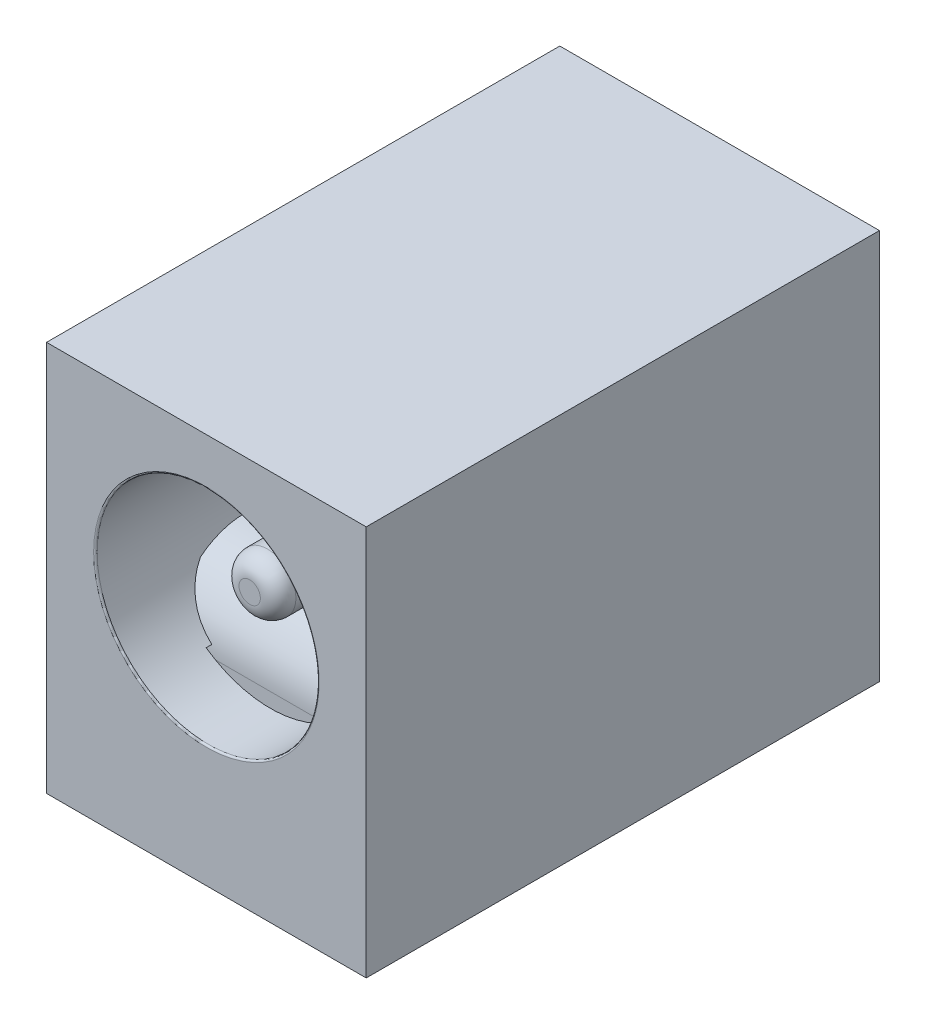
SolidWorks part; units mm, degrees
ref_plane "Plano frontal" through (0, 0, 0) normal (0, 0, 1) x (1, 0, 0)
ref_plane "Plano superior" through (0, 0, 0) normal (0, 1, 0) x (1, 0, 0)
ref_plane "Plano direito" through (0, 0, 0) normal (1, 0, 0) x (0, 0, -1)
sketch "Esboço1" plane through (0, 0, 0) normal (1, 0, 0) x (0, 0, -1)
  line L1 (-7.225, -5.5) -> (7.225, -5.5)
  line L2 (-7.225, -5.5) -> (-7.225, 5.5)
  line L3 (-7.225, 5.5) -> (7.225, 5.5)
  line L4 (7.225, -5.5) -> (7.225, 5.5)
  line L5 (-7.225, -5.5) -> (7.225, 5.5) construction
  line L6 (-7.225, 5.5) -> (7.225, -5.5) construction
  point P0 (0, 0)
  dimension "D1" = 11
  dimension "D2" = 14.45
extrude "Ressalto-extrusão1" add sketch "Esboço1" along normal blind 9
sketch "Esboço3" plane through (0, 0, 7.225) normal (0, 0, 1) x (1, 0, 0)
  line L0 (4.5, 5.5) -> (4.5, 4.175) construction
  line L1 (9, 5.5) -> (0, 5.5) construction
  line L3 (4.5, 1.05) -> (4.5, 5.5) construction
  circle A0 centre (4.5, 1.05) radius 3.125
  dimension "D1" = 6.25
  dimension "D2" = 4.45
extrude "Corte-extrusão2" cut sketch "Esboço3" against normal blind 8.93
sketch "Esboço4" plane through (0, 0, -1.705) normal (0, 0, 1) x (1, 0, 0)
  circle A2 centre (4.5, 1.05) radius 0.8
  dimension "D1" = 1.6
extrude "Ressalto-extrusão2" add sketch "Esboço4" along normal blind 7.71
fillet "Filete1" radius 0.5 1 edges at (5.3, 1.05, 6.005)
fillet "Filete2" radius 0.05 1 edges at (7.625, 1.05, 7.225)
sketch "Esboço5" plane through (0, -5.5, 0) normal (0, -1, 0) x (1, 0, 0)
  line L0 (4.5, 7.225) -> (4.5, 5.425) construction
  line L1 (9, 7.225) -> (0, 7.225) construction
  line L2 (1.5, 5.425) -> (7.5, 5.425)
  line L3 (1.5, 5.425) -> (1.5, -0.575)
  line L4 (1.5, -0.575) -> (7.5, -0.575)
  line L5 (7.5, -0.575) -> (7.5, 5.425)
  point P7 (4.5, 5.425)
  dimension "D1" = 1.8
  dimension "D2" = 6
  dimension "D3" = 6
extrude "Corte-extrusão5" cut sketch "Esboço5" against normal blind 4
sketch "Esboço7" plane through (0, -1.5, 0) normal (0, -1, 0) x (1, 0, 0)
  line L0 (4.5, 5.425) -> (4.5, -0.575) construction
  line L1 (7.5, 5.425) -> (1.5, 5.425) construction
  line L2 (1.5, -0.575) -> (7.5, -0.575) construction
  line L4 (1.6557, -0.4399) -> (7.3443, -0.4399)
  line L5 (1.6557, -0.4399) -> (1.6557, 5.2899)
  line L6 (1.6557, 5.2899) -> (7.3443, 5.2899)
  line L7 (7.3443, -0.4399) -> (7.3443, 5.2899)
  line L8 (1.6557, -0.4399) -> (7.3443, 5.2899) construction
  line L9 (1.6557, 5.2899) -> (7.3443, -0.4399) construction
  point P6 (4.5, 2.425)
extrude "Ressalto-extrusão4" add sketch "Esboço7" along normal blind 4 and the other way blind 1.7
fillet "Filete5" radius 2 1 edges at (4.5, 0.2, 5.2899)
chamfer "Chanfro4" distance 2 angle 45 1 edges at (4.5, 0.2, -0.4399)
fillet "Filete6" [suppressed] radius 1
sketch "Esboço9" [suppressed] plane through (0, -5.5, 0) normal (0, -1, 0) x (1, 0, 0)
  line L0 (4.5, 5.425) -> (4.5, -0.575) construction
  line L1 (7.5, 5.425) -> (1.5, 5.425) construction
  line L2 (1.5, -0.575) -> (7.5, -0.575) construction
  line L4 (1.9457, -0.3154) -> (7.0543, -0.3154)
  line L5 (1.9457, -0.3154) -> (1.9457, 5.1654)
  line L6 (1.9457, 5.1654) -> (7.0543, 5.1654)
  line L7 (7.0543, -0.3154) -> (7.0543, 5.1654)
  line L8 (1.9457, -0.3154) -> (7.0543, 5.1654) construction
  line L9 (1.9457, 5.1654) -> (7.0543, -0.3154) construction
  line L10 (1.5, -0.575) -> (7.5, -0.575)
  line L11 (1.5, -0.575) -> (1.5, 5.425)
  line L12 (1.5, 5.425) -> (7.5, 5.425)
  line L13 (7.5, -0.575) -> (7.5, 5.425)
  line L14 (1.5, -0.575) -> (7.5, 5.425) construction
  line L15 (1.5, 5.425) -> (7.5, -0.575) construction
  point P6 (4.5, 2.425)
  point P11 (4.5, 2.425)
extrude "Corte-extrusão6" [suppressed] cut sketch "Esboço9" against normal blind 4
sketch "Esboço11" [suppressed] plane through (0, -5.5, 0) normal (0, -1, 0) x (1, 0, 0)
  line L0 (4.5, 5.425) -> (4.5, -0.575) construction
  line L1 (7.5, 5.425) -> (1.5, 5.425) construction
  line L2 (1.5, -0.575) -> (7.5, -0.575) construction
  line L4 (1.323, -0.7753) -> (7.677, -0.7753)
  line L5 (1.323, -0.7753) -> (1.323, 5.6253)
  line L6 (1.323, 5.6253) -> (7.677, 5.6253)
  line L7 (7.677, -0.7753) -> (7.677, 5.6253)
  line L8 (1.323, -0.7753) -> (7.677, 5.6253) construction
  line L9 (1.323, 5.6253) -> (7.677, -0.7753) construction
  line L10 (1.9457, -0.3154) -> (7.0543, -0.3154)
  line L11 (1.9457, -0.3154) -> (1.9457, 5.1654)
  line L12 (1.9457, 5.1654) -> (7.0543, 5.1654)
  line L13 (7.0543, -0.3154) -> (7.0543, 5.1654)
  line L14 (1.9457, -0.3154) -> (7.0543, 5.1654) construction
  line L15 (1.9457, 5.1654) -> (7.0543, -0.3154) construction
  point P6 (4.5, 2.425)
  point P11 (4.5, 2.425)
extrude "Corte-extrusão7" [suppressed] cut sketch "Esboço11" against normal blind 5.7
sketch "Esboço13" [suppressed] plane through (0, 0, -7.225) normal (0, 0, -1) x (-1, 0, 0)
  line L0 (-11.3238, 1.01) -> (-10.8452, 6.8292)
  line L1 (-6.725, 5.04) -> (-2.275, 5.04)
  line L2 (-0.525, 1.01) -> (1.1221, 1.01)
  line L4 (-6.725, 5.04) -> (-2.275, 5.04)
  line L5 (-10.8452, 6.8292) -> (1.0427, 6.9871)
  line L8 (1.1221, 1.01) -> (1.0427, 6.9871)
  line L12 (-8.475, 1.01) -> (-11.3238, 1.01)
  line L13 (-2.275, 5.04) -> (-0.525, 1.01)
  line L14 (-6.725, 5.04) -> (-8.475, 1.01)
  point P3 (-4.5, 5.04)
  point P10 (-4.5, 5.04)
  dimension "D1" = 4.45
extrude "Corte-extrusão14" [suppressed] cut sketch "Esboço13" against normal blind 11.17 contours L14 L1 L13 L2 L0 L12
sketch "Esboço14" [suppressed] plane through (0, 5.5, 0) normal (0, 1, 0) x (1, 0, 0)
  line L3 (7, -5.01) -> (10.2146, -5.01)
  line L4 (-1.2146, -6.16) -> (2, -6.16)
  line L5 (-1.2146, -6.16) -> (-1.2146, -5.01)
  line L6 (-1.2146, -5.01) -> (2, -5.01)
  line L7 (10.2146, -6.16) -> (10.2146, -5.01)
  line L11 (2, -6.16) -> (2, -5.01)
  line L13 (7, -6.16) -> (7, -5.01)
  line L18 (7, -6.16) -> (10.2146, -6.16)
  point P6 (4.5, -5.585)
  point P11 (4.5, -5.585)
  dimension "D2" = 1.15
extrude "Corte-extrusão15" [suppressed] cut sketch "Esboço14" against normal blind 1
sketch "Esboço16" [suppressed] plane through (0, 0, -7.225) normal (0, 0, -1) x (-1, 0, 0)
  line L0 (-8.475, 1.01) -> (-8.475, 1.5435)
  line L1 (-8.475, 1.01) -> (-0.525, 1.01)
  line L2 (-0.525, 1.01) -> (-0.525, 1.5435)
  line L3 (-6.725, 5.04) -> (-8.475, 1.5435)
  line L4 (-6.725, 5.04) -> (-2.275, 5.04)
  line L6 (-2.275, 5.04) -> (-0.525, 1.5435)
extrude "Ressalto-extrusão5" [suppressed] add sketch "Esboço16" against normal blind 11.3
fillet "Filete7" [suppressed] radius 0.08
sketch "Esboço17" [suppressed] plane through (0, 0, 4.075) normal (0, 0, 1) x (1, 0, 0)
  line L0 (1.3762, 0.9625) -> (3.7048, 0.9625)
  line L1 (7.6219, 0.9102) -> (5.2786, 0.8664)
  arc A0 (7.6219, 0.9102) -> (1.3762, 0.9625) centre (4.5, 1.05) ccw
  arc A1 (5.2786, 0.8664) -> (3.7048, 0.9625) centre (4.5, 1.05) ccw
extrude "Corte-extrusão17" [suppressed] cut sketch "Esboço17" against normal blind 5.8
sketch "Esboço18" [suppressed] plane through (0, 0, -7.225) normal (0, 0, -1) x (-1, 0, 0)
  line L0 (-11.3995, -1.69) -> (1.4949, -1.69)
  line L1 (-8.92, -5.5) -> (-0.08, -5.5) construction
  line L2 (-11.3995, -1.69) -> (-11.0487, 7.356)
  line L3 (-11.0487, 7.356) -> (1.4949, 8.0327)
  line L4 (1.4949, 8.0327) -> (1.4949, -1.69)
  dimension "D1" = 3.81
extrude "Corte-extrusão18" [suppressed] cut sketch "Esboço18" against normal blind 0.97
sketch "Esboço19" [suppressed] plane through (0, 0, -6.255) normal (0, 0, -1) x (-1, 0, 0)
  line L0 (-8.92, -5.5) -> (-0.08, -5.5) construction
  line L1 (-5.995, -10.5806) -> (-3.005, -10.5806)
  line L2 (-5.995, -10.5806) -> (-5.995, -0.4194)
  line L3 (-5.995, -0.4194) -> (-3.005, -0.4194)
  line L4 (-3.005, -10.5806) -> (-3.005, -0.4194)
  line L5 (-5.995, -10.5806) -> (-3.005, -0.4194) construction
  line L6 (-5.995, -0.4194) -> (-3.005, -10.5806) construction
  point P0 (-4.5, -5.5)
  dimension "D1" = 2.99
extrude "Corte-extrusão19" [suppressed] cut sketch "Esboço19" along normal blind 0.97
sketch "Esboço20" [suppressed] plane through (0, 0, -6.255) normal (0, 0, -1) x (-1, 0, 0)
  line L3 (-5.825, -8.8251) -> (-3.175, -8.8251)
  line L4 (-5.825, -8.8251) -> (-5.825, -0.787)
  line L6 (-3.175, -8.8251) -> (-3.175, -0.787)
  arc A0 (-3.175, -0.787) -> (-5.825, -0.787) centre (-4.5, 1.05) ccw
  point P5 (-4.5, -2.5751)
  dimension "D3" = 4.53
  dimension "D2" = 2.65
extrude "Ressalto-extrusão6" [suppressed] add sketch "Esboço20" along normal blind 0.32
fillet "Filete8" [suppressed] radius 0.08
fillet "Filete9" [suppressed] radius 0.2
sketch "Esboço21" [suppressed] plane through (0, 0, -6.575) normal (0, 0, -1) x (-1, 0, 0)
  circle A0 centre (-4.4893, 1.1326) radius 1.3
  dimension "D1" = 2.6
extrude "Corte-extrusão20" [suppressed] cut sketch "Esboço21" against normal blind 0.22
chamfer "Chanfro5" [suppressed] distance 0.1 angle 45
sketch "Esboço22" [suppressed] plane through (0, 0, -6.355) normal (0, 0, -1) x (-1, 0, 0)
  circle A0 centre (-4.4893, 1.1326) radius 1.1934
extrude "Ressalto-extrusão8" [suppressed] add sketch "Esboço22" along normal blind 0.4
sketch "Esboço23" [suppressed] plane through (0, 0, -6.755) normal (0, 0, -1) x (-1, 0, 0)
  circle A0 centre (-4.4893, 1.1326) radius 0.5951
extrude "Corte-extrusão21" [suppressed] cut sketch "Esboço23" against normal blind 0.8
draft "Inclinação8" [suppressed] type of draft neutral plane draft angle 35 faces to draft 1 parameters "D1"=35
sketch "Esboço24" [suppressed] plane through (0, 0, -6.575) normal (0, 0, -1) x (-1, 0, 0)
  line L2 (-5.825, -6.8251) -> (-7.3072, -6.9926)
  line L4 (-7.3072, -6.9926) -> (-7.0269, -7.7009)
  line L5 (-7.0269, -7.7009) -> (-5.825, -7.8251)
  line L6 (-3.161, -6.8251) -> (-1.7002, -7.1697)
  line L8 (-5.825, -8.8251) -> (-5.825, -0.787) construction
  line L10 (-1.7002, -7.1697) -> (-2.4306, -7.5238)
  line L11 (-2.4306, -7.5238) -> (-2.5017, -7.8251)
  line L12 (-2.5017, -7.8251) -> (-3.161, -7.8251)
  arc A0 (-3.161, -6.8251) -> (-3.161, -7.8251) centre (-2.6839, -7.3251) ccw
  arc A1 (-5.825, -6.8251) -> (-5.825, -7.8251) centre (-6.35, -7.3251) cw
  point P0 (-4.5037, -7.3251)
extrude "Corte-extrusão22" [suppressed] cut sketch "Esboço24" against normal blind 0.8
sketch "Esboço26" [suppressed] plane through (0, 0, -6.575) normal (0, 0, -1) x (-1, 0, 0)
  line L0 (-5.825, -7.8251) -> (-4.5, -8.8251)
  line L1 (-3.175, -8.8251) -> (-5.825, -8.8251) construction
  line L2 (-3.175, -7.8114) -> (-4.5, -8.8251)
  line L3 (-5.825, -7.8251) -> (-7.9617, -7.8251)
  line L4 (-7.9617, -7.8251) -> (-7.2712, -9.4826)
  line L5 (-7.2712, -9.4826) -> (-3.8361, -10.0138)
  line L6 (-3.8361, -10.0138) -> (-2.335, -9.3883)
  line L7 (-2.335, -9.3883) -> (-1.7907, -8.0667)
  line L8 (-1.7907, -8.0667) -> (-3.175, -7.8114)
extrude "Corte-extrusão23" [suppressed] cut sketch "Esboço26" against normal blind 0.8
sketch "Esboço27" [suppressed] plane through (0, 0, -6.575) normal (0, 0, -1) x (-1, 0, 0)
  line L0 (-4.5, 3.115) -> (-4.5, -8.8251) construction
  line L1 (-4.5, -8.8251) -> (-4.2386, -8.6251) construction
  arc A0 (-3.375, -0.6816) -> (-5.625, -0.6816) centre (-4.5, 1.05) ccw construction
  circle A1 centre (-4.5, -3.285) radius 0.4953
  arc A2 (-3.175, -0.787) -> (-5.825, -0.787) centre (-4.5, 1.05) ccw construction
  point P13 (-4.5, 3.315)
  dimension "D1" = 6.6
  dimension "D2" = 0.9907
extrude "Corte-extrusão24" [suppressed] cut sketch "Esboço27" against normal blind 1.3
fillet "Filete10" [suppressed] radius 0.2
sketch "Esboço28" [suppressed] plane through (0, 0, 0) normal (-1, 0, 0) x (0, 0, 1)
  line L1 (-5.4377, -1.8018) -> (-3.4377, -1.8018)
  line L2 (-5.4377, -1.8018) -> (-5.4377, -1.6304)
  line L3 (-5.4377, -1.6304) -> (-3.4377, -1.6304)
  line L4 (-3.4377, -1.8018) -> (-3.4377, -1.6304)
  line L5 (-5.4377, -1.8018) -> (-3.4377, -1.6304) construction
  line L6 (-5.4377, -1.6304) -> (-3.4377, -1.8018) construction
  point P0 (-4.4377, -1.7161)
  dimension "D1" = 2
extrude "Ressalto-extrusão9" [suppressed] add sketch "Esboço28" along normal blind 0.005
sketch "Esboço29" [suppressed] plane through (0, 0, 0) normal (-1, 0, 0) x (0, 0, 1)
  line L0 (-4.4377, -1.7161) -> (-4.4377, -1.8018) construction
  line L2 (-5.4377, -1.8018) -> (-3.4377, -1.8018) construction
  line L4 (-5.4527, -1.8161) -> (-3.4227, -1.8161)
  line L5 (-5.4527, -1.8161) -> (-5.4527, -1.6161)
  line L6 (-5.4527, -1.6161) -> (-3.4227, -1.6161)
  line L7 (-3.4227, -1.8161) -> (-3.4227, -1.6161)
  line L10 (-5.4827, -1.8461) -> (-3.3927, -1.8461)
  line L11 (-5.4827, -1.8461) -> (-5.4827, -1.5861)
  line L12 (-5.4827, -1.5861) -> (-3.3927, -1.5861)
  line L13 (-3.3927, -1.8461) -> (-3.3927, -1.5861)
  point P6 (-4.4377, -1.7161)
  point P11 (-4.4377, -1.7161)
  dimension "D1" = 2.03
  dimension "D2" = 0.2
  dimension "D3" = 0.26
  dimension "D4" = 2.09
extrude "Corte-extrusão26" [suppressed] cut sketch "Esboço29" against normal blind 0.005
sketch "Esboço31" [suppressed] plane through (0, -5.5, 0) normal (0, -1, 0) x (1, 0, 0)
  line L0 (6.2864, -4.42) -> (6.2864, -1.2948)
  line L2 (-0.4074, -4.445) -> (2.7243, -4.445) construction
  line L3 (-0.4074, -4.445) -> (2.7243, -4.445)
  line L4 (-0.4074, -4.42) -> (2.6833, -4.42)
  line L5 (-0.4074, -4.42) -> (-0.4074, -4.445)
  line L6 (10.12, -4.42) -> (10.12, -4.445)
  line L7 (6.2864, -1.2948) -> (2.6833, -1.2948)
  line L8 (2.7243, -4.42) -> (2.7243, -4.445)
  line L9 (2.6833, -4.42) -> (2.6833, -1.2948)
  line L10 (2.7243, -4.445) -> (2.7243, -1.325)
  line L11 (2.7243, -4.445) -> (2.7243, -4.42)
  line L12 (2.7243, -1.325) -> (6.2543, -1.325)
  line L13 (6.2543, -4.445) -> (6.2543, -4.42)
  line L17 (6.2543, -4.445) -> (6.2543, -1.325)
  line L18 (6.2543, -4.42) -> (6.2543, -4.445)
  line L19 (6.2543, -4.445) -> (10.12, -4.445)
  line L21 (2.7243, -4.445) -> (-0.4074, -4.445) construction
  line L22 (6.2864, -4.42) -> (10.12, -4.42)
  line L23 (6.2543, -4.445) -> (10.12, -4.445) construction
  point P9 (4.4893, -4.8459)
  line M19 (8.92, -7.225) -> (8.92, 7.145)
  line M21 (0.08, 7.145) -> (0.08, -7.225)
extrude "Corte-extrusão27" [suppressed] cut sketch "Esboço31" against normal blind 0.2 contours L22 L0 L7 L9 L4 L3 L8 L10 L12 L17 L13 L19 M21 M19
sketch "Esboço33" [suppressed] plane through (0, -5.5, 0) normal (0, -1, 0) x (1, 0, 0)
  point P2 (4.5, -3.35)
  point P7 (4.5, -3.35)
sketch "Esboço35" [suppressed] plane through (0, -5.5, 0) normal (0, -1, 0) x (1, 0, 0)
  line L0 (0.5558, -4.445) -> (8.4442, -4.445)
  line L2 (0.5558, -4.445) -> (0.5558, 6.8107)
  line L3 (0.5558, 6.8107) -> (8.4442, 6.8107)
  line L4 (8.4442, -4.445) -> (8.4442, 6.8107)
  line L7 (0.08, -4.445) -> (2.7243, -4.445) construction
  point P0 (4.5, -3.35)
extrude "Ressalto-extrusão10" [suppressed] add sketch "Esboço35" against normal blind 3.2
sketch "Esboço36" [suppressed] plane through (0, -5.5, 0) normal (0, -1, 0) x (1, 0, 0)
  line L0 (0.6368, -4.4023) -> (-0.0867, -4.4023)
  line L1 (6.765, -4.4023) -> (6.765, -0.125)
  line L2 (-0.0867, -4.4425) -> (2.275, -4.4425)
  line L4 (6.765, -4.4023) -> (11.2265, -4.4023)
  line L5 (6.725, -4.4425) -> (10.9091, -4.4425)
  line L6 (2.235, -0.125) -> (6.765, -0.125)
  line L7 (2.275, -0.165) -> (6.725, -0.165)
  line L9 (-0.0867, -4.4425) -> (-0.0867, -4.4023)
  line L10 (0.6368, -4.4023) -> (2.235, -4.4023)
  line L11 (11.2265, -4.4023) -> (10.9091, -4.4425)
  line L12 (2.275, -4.4425) -> (2.275, -0.165)
  line L13 (2.235, -4.4023) -> (2.235, -0.125)
  line L15 (6.725, -4.4425) -> (6.725, -0.165)
  point P5 (4.5, -7.225)
  dimension "D2" = 0.04
  dimension "D3" = 0.04
extrude "Corte-extrusão29" [suppressed] cut sketch "Esboço36" against normal blind 0.2
sketch "Esboço37" [suppressed] plane through (0, -5.5, 0) normal (0, -1, 0) x (1, 0, 0)
  line L0 (3.005, -0.125) -> (5.995, -0.125)
  line L1 (5.995, -0.445) -> (5.995, -0.125)
  line L2 (5.995, -0.445) -> (3.005, -0.445)
  line L3 (3.005, -0.445) -> (3.005, -0.125)
  point P17 (4.5, -0.285)
  dimension "D3" = 2.99
extrude "Corte-extrusão30" [suppressed] cut sketch "Esboço37" against normal blind 0.2
sketch "Esboço38" [suppressed] plane through (0, -5.3, 0) normal (0, -1, 0) x (1, 0, 0)
  line L0 (4.5, -0.125) -> (4.5, -0.445) construction
  line L1 (6.765, -0.125) -> (2.235, -0.125) construction
  line L2 (3.005, -0.445) -> (5.995, -0.445) construction
  line L4 (3.0256, -0.4261) -> (5.9744, -0.4261)
  line L5 (3.0256, -0.4261) -> (3.0256, -0.1439)
  line L6 (3.0256, -0.1439) -> (5.9744, -0.1439)
  line L7 (5.9744, -0.4261) -> (5.9744, -0.1439)
  line L8 (3.0256, -0.4261) -> (5.9744, -0.1439) construction
  line L9 (3.0256, -0.1439) -> (5.9744, -0.4261) construction
  point P6 (4.5, -0.285)
extrude "Ressalto-extrusão15" [suppressed] add sketch "Esboço38" along normal blind 3.3
sketch "Esboço39" [suppressed] plane through (0, 0, -0.4261) normal (0, 0, -1) x (-1, 0, 0)
  line L0 (-5.995, -5.5) -> (-5.825, -5.5)
  line L1 (-5.825, -5.5) -> (-5.825, -6.8251)
  line L3 (-5.825, -7.8251) -> (-4.765, -8.6251)
  line L4 (-4.765, -8.6251) -> (-4.2386, -8.6251)
  line L5 (-4.2386, -8.6251) -> (-3.175, -7.8114)
  line L7 (-3.175, -6.8251) -> (-3.175, -5.5)
  line L8 (-3.175, -0.787) -> (-3.175, -6.8389) construction
  line L9 (-3.175, -5.5) -> (-3.005, -5.5)
  line L10 (-3.005, -5.5) -> (-2.161, -7.3183)
  line L11 (-2.161, -7.3183) -> (-2.2525, -9.6728)
  line L12 (-2.2525, -9.6728) -> (-5.295, -10.0387)
  line L13 (-5.295, -10.0387) -> (-7.4366, -9.1646)
  line L14 (-7.4366, -9.1646) -> (-7.5993, -6.5522)
  line L15 (-7.5993, -6.5522) -> (-5.995, -5.5)
  arc A0 (-5.625, -7.3251) -> (-5.825, -6.8251) centre (-6.35, -7.3251) ccw construction
  arc A1 (-5.825, -7.8251) -> (-5.625, -7.3251) centre (-6.35, -7.3251) ccw construction
  arc A2 (-5.825, -6.8251) -> (-5.825, -7.8251) centre (-6.35, -7.3251) cw
  arc A3 (-3.175, -6.8251) -> (-3.175, -7.8114) centre (-2.6672, -7.3183) ccw
extrude "Corte-extrusão31" [suppressed] cut sketch "Esboço39" against normal blind 3.3
sketch "Esboço40" [suppressed] plane through (0, 0, -6.255) normal (0, 0, 1) x (1, 0, 0)
  line L0 (4.7983, -8.6) -> (4.1126, -8.6)
  line L1 (4.1126, -8.6) -> (4.3448, -8.9735)
  line L2 (4.3448, -8.9735) -> (4.8373, -9.0415)
  line L3 (4.8373, -9.0415) -> (5.0535, -8.6852)
  line L4 (5.0535, -8.6852) -> (4.7983, -8.6)
extrude "Corte-extrusão32" [suppressed] cut sketch "Esboço40" against normal blind 15.3
fillet "Filete13" [suppressed] radius 0.1
fillet "Filete14" [suppressed] radius 0.1
sketch "Esboço41" [suppressed] plane through (0, -5.5, 0) normal (0, -1, 0) x (1, 0, 0)
  line L5 (9.4111, -4.8545) -> (9.0911, -4.8545)
  line L6 (9.4111, -4.8545) -> (9.4111, -1.8645)
  line L7 (9.4111, -1.8645) -> (9.0911, -1.8645)
  line L8 (9.0911, -4.8545) -> (9.0911, -1.8645)
  line L10 (3.005, -0.445) -> (5.995, -0.445) construction
  dimension "D1" = 0.32
  dimension "D2" = 2.99
extrude "Ressalto-extrusão16" [suppressed] add sketch "Esboço41" against normal blind 4.3 and the other way blind 3.12 separate body
sketch "Esboço42" [suppressed] plane through (9.0911, 0, 0) normal (-1, 0, 0) x (0, 0, 1)
  line L0 (-4.8545, -1.2) -> (-1.8645, -1.2) construction
  line L2 (-1.8645, -1.2) -> (-1.8645, -1.52)
  line L3 (-1.8645, -1.52) -> (-4.8545, -1.52)
  line L4 (-4.8545, -1.2) -> (-4.8545, -1.52)
  line L7 (-4.8545, -8.62) -> (-4.8545, -1.2) construction
  line L8 (-1.8645, -1.2) -> (-4.8545, -1.2)
  point P0 (-3.3595, -1.2)
extrude "Ressalto-extrusão17" [suppressed] add sketch "Esboço42" along normal blind 0.5
fillet "Filete16" [suppressed] radius 0.2
sketch "Esboço44" [suppressed] plane through (9.4111, 0, 0) normal (1, 0, 0) x (0, 0, -1)
  line L1 (1.8635, -6.7866) -> (1.1836, -6.7866)
  line L2 (1.1836, -6.7866) -> (1.1836, -9.6614)
  line L3 (1.8645, -8.62) -> (1.8645, -1.4) construction
  line L4 (3.3595, -8.62) -> (3.0195, -8.62)
  line L5 (4.8545, -8.62) -> (4.8545, -1.4) construction
  line L6 (4.8545, -8.62) -> (1.8645, -8.62) construction
  line L7 (3.0195, -8.62) -> (1.8645, -7.8083)
  line L8 (3.3595, -8.62) -> (3.6995, -8.62)
  line L9 (3.6995, -8.62) -> (4.8545, -7.8083)
  line L10 (1.1836, -9.6614) -> (6.1111, -9.9192)
  line L11 (6.1111, -9.9192) -> (5.529, -7.0169)
  line L12 (5.529, -7.0169) -> (5.6454, -6.7092)
  line L13 (5.6454, -6.7092) -> (4.8545, -6.7866)
  arc A0 (1.8635, -6.7866) -> (1.8645, -7.8083) centre (1.1836, -7.2981) cw
  arc A1 (4.8545, -7.8083) -> (4.8545, -6.7866) centre (5.6994, -7.2975) cw
  point P7 (3.3595, -8.62)
  point P18 (3.3595, -8.62)
  dimension "D1" = 0.34
  dimension "D2" = 0.34
extrude "Corte-extrusão33" [suppressed] cut sketch "Esboço44" against normal blind 0.5
fillet "Filete17" [suppressed] radius 0.2
fillet "Filete18" [suppressed] radius 0.2
sketch "Esboço45" [suppressed] plane through (0, 0, -7.225) normal (0, 0, -1) x (-1, 0, 0)
  line L0 (-8.475, 1.01) -> (-8.475, 1.4165)
  line L3 (-8.475, 1.01) -> (-8.475, -6.866)
  line L4 (-0.525, 1.01) -> (-0.525, 1.4165)
  line L5 (-8.475, -4.11) -> (-8.475, 1.01)
  line L6 (-0.525, 1.4165) -> (1.4123, 1.4165)
  line L7 (-0.525, 1.4165) -> (-0.525, 1.01)
  line L8 (-0.525, 1.4165) -> (-0.525, -6.9774)
  line L10 (-8.475, -6.866) -> (-9, -6.866)
  line L11 (-9, -6.866) -> (-9, 1.4165)
  line L12 (-9, 1.4165) -> (-8.475, 1.4165)
  line L13 (-0.525, 1.4165) -> (-0.525, 1.01)
  line L14 (-0.525, -6.9774) -> (0.7808, -6.9774)
  line L15 (0.7808, -6.9774) -> (1.4123, 1.4165)
  point P6 (-4.5, -1.55)
  line M3 (-3.005, -5.5) -> (-0.08, -5.5)
  line M4 (-0.08, -5.5) -> (-0.08, -1.69)
  line M5 (-0.08, -1.69) -> (-3.005, -1.69)
extrude "Corte-extrusão38" [suppressed] cut sketch "Esboço45" against normal blind 1.4 contours L14 L15 L6 L4 L8 M5 M4 M3 | L12 L11 L10 L3 L0
sketch "Esboço47" [suppressed] plane through (0, 0, -5.825) normal (0, 0, -1) x (-1, 0, 0)
  line L0 (-0.525, 1.01) -> (-0.525, -6.4003)
  line L1 (-0.525, -6.4003) -> (0.4607, -6.4003)
  line L2 (0.4607, -6.4003) -> (0.3762, 1.01)
  line L3 (0.3762, 1.01) -> (-0.525, 1.01)
extrude "Corte-extrusão39" [suppressed] cut sketch "Esboço47" along normal blind 13.4
fillet "Filete19" [suppressed] radius 0.05
sketch "Esboço48" [suppressed] plane through (7.0543, 0, 0) normal (1, 0, 0) x (0, 0, -1)
  line L0 (-5.1654, -2.3) -> (-5.0783, -1.7386)
  line L1 (-5.0783, -1.7386) -> (-2.425, 0.2)
  line L2 (0.7753, 0.2) -> (-5.6253, 0.2) construction
  line L3 (-2.425, 0.2) -> (-0.9271, -0.287)
  line L4 (-0.9271, -0.287) -> (0.3154, -1.6756)
  line L5 (0.3154, -1.6756) -> (0.3154, -2.2721)
  line L6 (0.3154, -1.6756) -> (0.3154, -2.3) construction
  line L7 (0.3154, -2.2721) -> (0.3878, -2.3)
  line L8 (0.7753, -2.3) -> (-5.6253, -2.3) construction
  line L9 (0.3878, -2.3) -> (0.3878, -1.5252)
  line L10 (0.3878, -1.5252) -> (-0.9271, -0.2103)
  line L11 (-4.8415, -0.2584) -> (-4.4711, 0.112)
  line L12 (-0.9271, -0.2103) -> (-1.4872, 0.2375)
  line L14 (-4.4711, 0.112) -> (-3.65, 0.2375)
  line L15 (-4.8415, -0.2584) -> (-5.3324, -0.4426)
  line L16 (-5.3324, -0.4426) -> (-5.4103, -2.1039)
  line L17 (-5.4103, -2.1039) -> (-5.1654, -2.3)
  line L18 (-1.4872, 0.2375) -> (-3.65, 0.2375)
extrude "Corte-extrusão42" [suppressed] cut sketch "Esboço48" against normal blind 5.13
